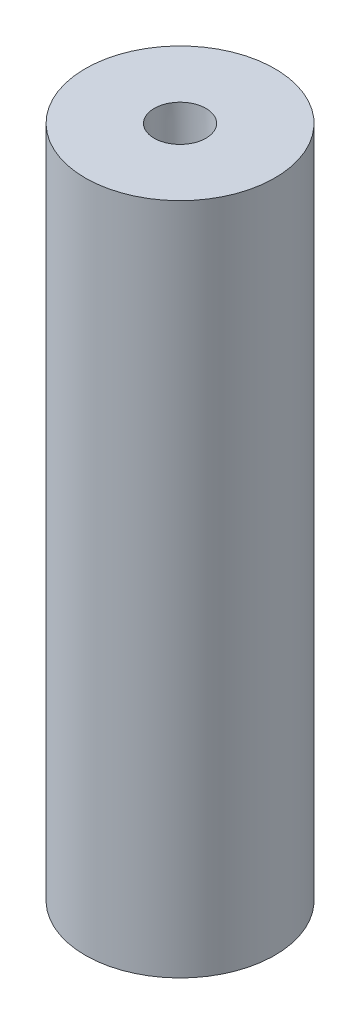
SolidWorks part; units mm, degrees
ref_plane "Front Plane" through (0, 0, 0) normal (0, 0, 1) x (1, 0, 0)
ref_plane "Top Plane" through (0, 0, 0) normal (0, 1, 0) x (1, 0, 0)
ref_plane "Right Plane" through (0, 0, 0) normal (1, 0, 0) x (0, 0, -1)
sketch "Sketch1" plane through (0, 0, 0) normal (0, 1, 0) x (1, 0, 0)
  circle A0 centre (0, 0) radius 9.15
  dimension "D1" = 18.3
extrude "Boss-Extrude1" add sketch "Sketch1" along normal blind 65
sketch "Sketch2" plane through (0, 65, 0) normal (0, 1, 0) x (1, 0, 0)
  circle A0 centre (0, 0) radius 2.5
  dimension "D1" = 5
extrude "Cut-Extrude1" cut sketch "Sketch2" against normal blind 10
chamfer "Chamfer1" distance 10 distance2 0.25 1 edges at (0, 55, 2.5) first distance on face at (0, 55, 2.5)
sketch "Sketch3" plane through (0, 0, 0) normal (0, -1, 0) x (1, 0, 0)
  circle A0 centre (0, 0) radius 2.5
  dimension "D1" = 5
extrude "Cut-Extrude2" cut sketch "Sketch3" against normal blind 10
chamfer "Chamfer2" distance 10 distance2 0.25 1 edges at (0, 10, -2.5) first distance on face at (0, 10, -2.5)
